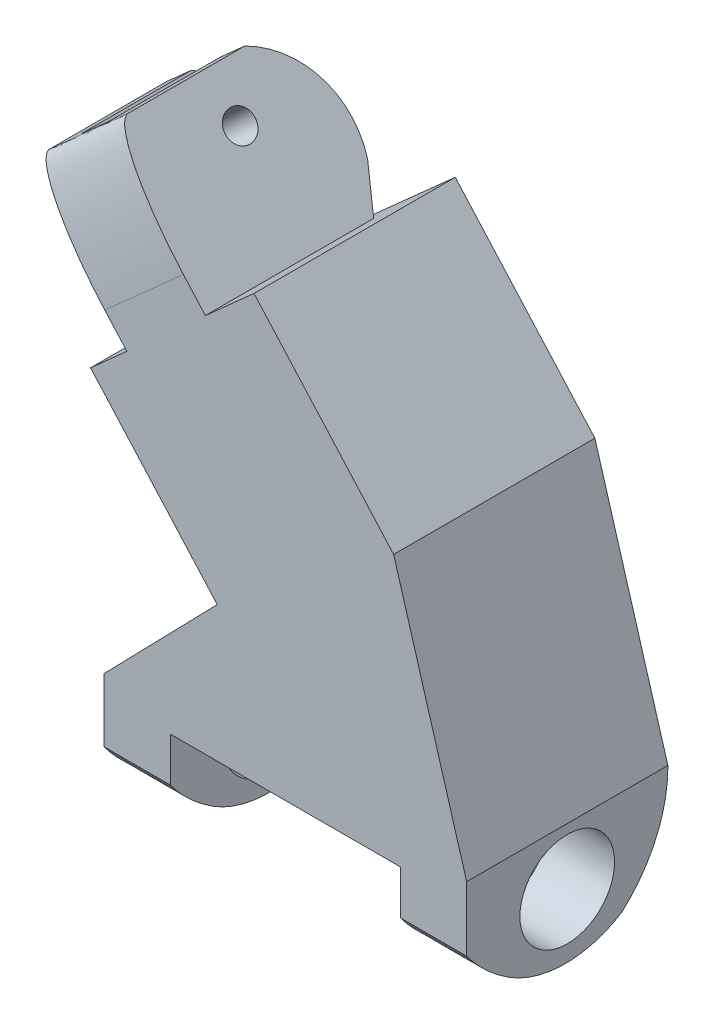
SolidWorks part; units mm, degrees
ref_plane "Plan de face" through (0, 0, 0) normal (0, 0, 1) x (1, 0, 0)
ref_plane "Plan de dessus" through (0, 0, 0) normal (0, 1, 0) x (1, 0, 0)
ref_plane "Plan de droite" through (0, 0, 0) normal (1, 0, 0) x (0, 0, -1)
sketch "Sketch1" plane through (0, 0, 0) normal (0, 0, 1) x (1, 0, 0)
  line L0 (0, 0) -> (-11.7972, 13.1953)
  line L1 (-11.7972, 13.1953) -> (-15.9072, 9.5208)
  line L2 (-15.9072, 9.5208) -> (-24.4319, 19.0557)
  line L3 (-24.4319, 19.0557) -> (-31.0668, 13.1237)
  line L4 (-31.0668, 13.1237) -> (-22.5421, 3.5888)
  line L5 (-22.5421, 3.5888) -> (-25.6061, 0.8495)
  line L6 (-25.6061, 0.8495) -> (-14.9041, -11.1209)
  line L7 (-14.9041, -11.1209) -> (-24.4642, -20.9478)
  line L8 (-24.4642, -20.9478) -> (-24.4642, -31.4378)
  line L9 (-24.4642, -31.4378) -> (-18.8642, -31.4378)
  line L10 (-18.8642, -31.4378) -> (-18.8642, -22.5778)
  line L11 (-18.8642, -22.5778) -> (0.5658, -22.5778)
  line L12 (0.5658, -22.5778) -> (0.5658, -31.4378)
  line L13 (0.5658, -31.4378) -> (6.1658, -31.4378)
  line L14 (6.1658, -31.4378) -> (6.1658, -20.8578)
  line L15 (6.1658, -20.8578) -> (0, 0)
  point P16 (-32.721, -6.6896)
  point P18 (-22.1377, -61.0698)
  point P19 (-28.18, -51.5749)
  point P20 (13.0109, -27.6524)
  point P21 (13.0109, -68.9451)
  point P22 (-13.2395, -28.2423)
  point P23 (-8.2254, -30.3069)
  point P24 (19.1967, -45.1663)
  point P25 (14.9976, -30.5694)
  point P26 (-7.7976, -18.7719)
  point P27 (-16.1563, -10.1737)
  dimension "D1" = 8.9
  dimension "D2" = 12.79
  dimension "D3" = 12.79
  dimension "D4" = 93.99
  dimension "D5" = 5.6
  dimension "D6" = 5.6
  dimension "D7" = 19.43
  dimension "D8" = 8.86
  dimension "D9" = 8.86
  dimension "D10" = 4.11
  dimension "D11" = 4.11
  dimension "D12" = 90
  dimension "D13" = 17.7
  dimension "D14" = 154.67
  dimension "D15" = 21.75
  dimension "D16" = 10.58
  dimension "D17" = 10.49
  dimension "D18" = 13.71
extrude "Boss-Extrude1" add sketch "Sketch1" along normal blind 17
sketch "Sketch3" plane through (-4.11, -3.6745, 0) normal (0.7455, 0.6665, 0) x (0, 0, -1)
  line L0 (-1.1105, 20.9807) -> (-2.78, 17.7)
  line L1 (-17, 17.7) -> (0, 17.7) construction
  line L2 (-2.78, 17.7) -> (0.68, 17.7)
  line L3 (0.68, 17.7) -> (0.68, 32.5691)
  line L4 (0.68, 32.5691) -> (-17, 32.5691)
  line L5 (-17, 32.5691) -> (-17, 30.49)
  line L6 (-17, 30.49) -> (-5.15, 30.49)
  line L7 (-17, 30.49) -> (0, 30.49) construction
  line L8 (-17, 0) -> (-17, 17.7) construction
  arc A0 (-1.1105, 20.9807) -> (-5.15, 30.49) centre (-8.336, 23.524) ccw
  dimension "D5" = 7.66
  dimension "D1" = 11.85
  dimension "D2" = 3.46
  dimension "D3" = 17.68
  dimension "D4" = 63.03
extrude "Cut-Extrude2" cut sketch "Sketch3" against normal blind 35
sketch "Sketch4" plane through (-18.8642, 0, 0) normal (1, 0, 0) x (0, 0, -1)
  line L1 (-17, -31.4378) -> (-17, -22.5778) construction
  line L2 (-17, -26.3078) -> (-17, -22.5778)
  line L3 (-17, -22.5778) -> (-18.3389, -22.5778)
  line L4 (-18.3389, -22.5778) -> (-18.3389, -32.3097)
  line L5 (-18.3389, -32.3097) -> (1.1376, -32.3097)
  line L6 (1.1376, -32.3097) -> (1.1376, -22.5778)
  line L7 (1.1376, -22.5778) -> (0, -22.5778)
  line L8 (0, -22.5778) -> (0, -29.6578)
  line L9 (0, -31.4378) -> (0, -22.5778) construction
  line L10 (0, -29.6578) -> (-3.9, -29.6578)
  arc A1 (-3.9, -29.6578) -> (-13.4, -29.6578) centre (-8.65, -22.1313) cw
  spline S0 degree 2 poles (-13.4, -29.6578) (-15.5415, -28.2985) (-17, -26.3078) knots 0 0 0 1 1 1
  dimension "D5" = 8.9
  dimension "D1" = 3.9
  dimension "D2" = 3.73
  dimension "D3" = 7.08
  dimension "D4" = 9.5
  dimension "D6" = 3.6
extrude "Cut-Extrude3" cut sketch "Sketch4" against normal mid plane 61
sketch "Sketch5" plane through (0.5658, 0, 0) normal (-1, 0, 0) x (0, 0, 1)
  line L0 (3.9, -29.6578) -> (0, -29.6578)
  line L1 (0, -29.6578) -> (0, -20.9478)
  arc A0 (3.9, -29.6578) -> (0, -20.9478) centre (11.6762, -20.9478) cw
extrude "Cut-Extrude4" cut sketch "Sketch5" against normal blind 61
sketch "Sketch6" plane through (-24.4642, 0, 0) normal (-1, 0, 0) x (0, 0, 1)
  line L0 (0, -29.6578) -> (3.9, -29.6578) construction
  circle A0 centre (8.5, -25.6578) radius 4
  dimension "D3" = 8
  dimension "D1" = 4
  dimension "D2" = 8.5
extrude "Cut-Extrude5" cut sketch "Sketch6" against normal blind 61
sketch "Sketch7" plane through (-20.3219, 22.7302, 0) normal (-0.6665, 0.7455, 0) x (0.7455, 0.6665, 0)
  line L0 (-9.9631, -17) -> (-9.9631, -12.2961) construction
  line L1 (-5.5131, -17) -> (-14.4131, -17) construction
  line L2 (-11.6131, -14.5) -> (-8.3131, -14.5)
  line L3 (-11.6131, -14.5) -> (-11.6131, -0.2987)
  line L4 (-11.6131, -0.2987) -> (-8.3131, -0.2987)
  line L5 (-8.3131, -14.5) -> (-8.3131, -0.2987)
  point P6 (-9.9631, -17)
  point P9 (-9.9631, -14.5)
  dimension "D1" = 3.3
  dimension "D2" = 1.65
  dimension "D3" = 2.5
extrude "Cut-Extrude6" cut sketch "Sketch7" against normal up to surface (12.79 mm away) up to face at (-18.9632, 6.7886, 9.195)
sketch "Sketch8" plane through (-10.7449, -9.6065, 0) normal (-0.7455, -0.6665, 0) x (0, 0, 1)
  line L0 (17, 30.49) -> (17, 17.7) construction
  line L1 (17, 30.49) -> (5.15, 30.49) construction
  circle A0 centre (8.2, 26.49) radius 1.25
  dimension "D3" = 2.5
  dimension "D1" = 8.8
  dimension "D2" = 4
extrude "Cut-Extrude7" cut sketch "Sketch8" against normal blind 61
ref_plane "Plane1" through (-7.4275, -6.6405, 0) normal (-0.7455, -0.6665, 0) x (0, 0, 1)
sketch "Sketch9" plane through (-7.4275, -6.6405, 0) normal (-0.7455, -0.6665, 0) x (0, 0, 1)
  circle A0 centre (8.2, 26.49) radius 1.25
extrude "Extrude-Thin1" add sketch "Sketch9" along normal blind 1.75 draft 30 and the other way blind 1.75 draft 30 thin draft outward yes other way draft outward yes thin type one direction wall 1
sketch "Sketch10" plane through (-4.11, -3.6745, 0) normal (0.7455, 0.6665, 0) x (0, 0, -1)
  circle A0 centre (-8.2, 26.49) radius 1.25
extrude "Cut-Extrude9" cut sketch "Sketch10" against normal through all
fillet "Fillet1" radius 2 1 edges at (-27.7493, 16.0897, 17) second distance 10 first distance on face at (-27.7493, 16.0897, 10.45)
